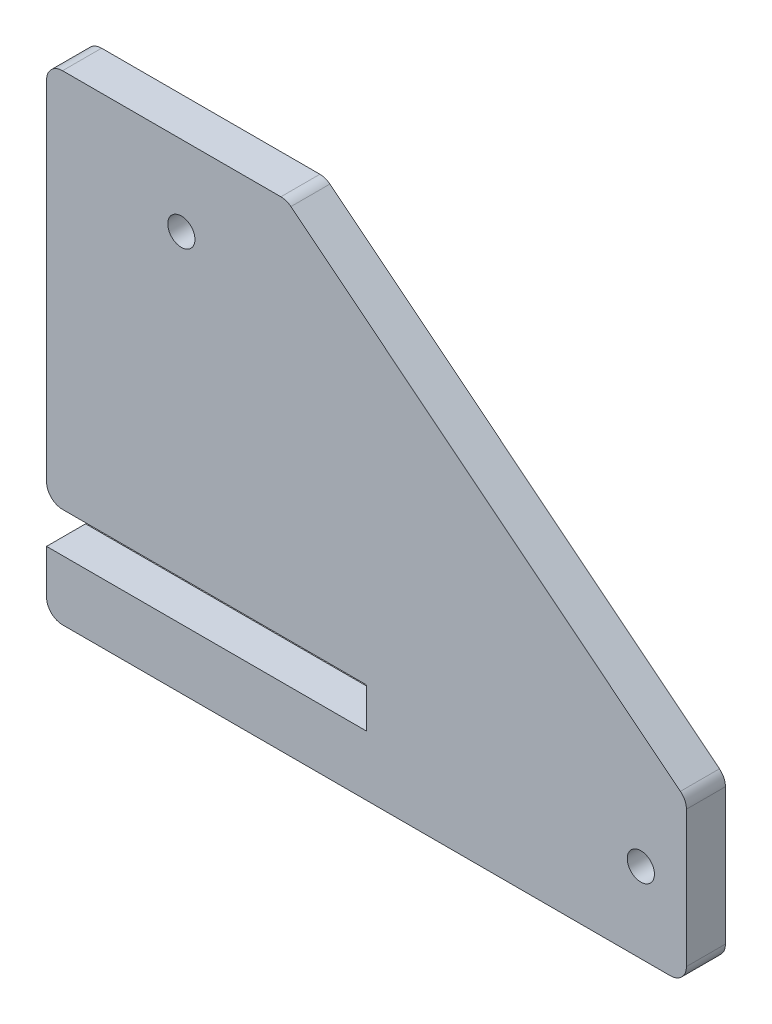
SolidWorks part; units mm, degrees
material "Corrugated Paper"
ref_plane "Front Plane" through (0, 0, 0) normal (0, 0, 1) x (1, 0, 0)
ref_plane "Top Plane" through (0, 0, 0) normal (0, 1, 0) x (1, 0, 0)
ref_plane "Right Plane" through (0, 0, 0) normal (1, 0, 0) x (0, 0, -1)
sketch "Sketch1" plane through (0, 0, 0) normal (0, 0, 1) x (1, 0, 0)
  line L0 (-25.4, 1.5875) -> (-25.4, 6.35)
  line L1 (-25.4, -1.5875) -> (0, -1.5875)
  line L3 (-25.4, 1.5875) -> (0, 1.5875)
  line L4 (0, -1.5875) -> (0, 1.5875)
  line L5 (-25.4, 6.35) -> (25.4, 6.35)
  line L6 (0, 0) -> (25.4, 0) construction
  line L7 (25.4, 6.35) -> (25.4, -6.35)
  line L8 (-25.4, -6.35) -> (25.4, -6.35)
  line L9 (-25.4, -1.5875) -> (-25.4, -6.35)
  line L11 (-25.4, 6.35) -> (25.4, 6.35)
  line L12 (-25.4, 6.35) -> (-25.4, 31.75)
  line L13 (-25.4, 31.75) -> (25.4, 31.75)
  line L14 (25.4, 6.35) -> (25.4, 31.75)
  dimension "D1" = 25.4
  dimension "D2" = 3.175
  dimension "D3" = 25.4
  dimension "D4" = 12.7
  dimension "D5" = 38.1
extrude "Boss-Extrude1" add sketch "Sketch1" along normal mid plane 3.0988 contours L5 L14 L13 L12 | L6 L4 L1 L9 L8 L7 | L4 L6 L7 L5 L0 L3 region at (1.8143, 3.5152, 0) region at (0, 19.05, 0) region at (1.8143, -3.5152, 0)
sketch "Sketch2" plane through (0, 0, 1.5494) normal (0, 0, 1) x (1, 0, 0)
  line L0 (0, 0) -> (25.4, 0) construction
  line L2 (25.4, -6.35) -> (25.4, 31.75) construction
  circle A0 centre (21.7805, 0) radius 1.0795
  dimension "D1" = 2.159
extrude "Cut-Extrude1" cut sketch "Sketch2" against normal through all
sketch "Sketch3" plane through (0, 0, 1.5494) normal (0, 0, 1) x (1, 0, 0)
  circle A0 centre (-14.6975, 25.4) radius 1.0795
  circle A1 centre (21.7805, 0) radius 1.0795 construction
  dimension "D1" = 44.45
  dimension "D2" = 25.4
extrude "Cut-Extrude2" cut sketch "Sketch3" against normal through all
sketch "Sketch4" plane through (0, 0, 1.5494) normal (0, 0, 1) x (1, 0, 0)
  line L0 (-6.35, 31.75) -> (25.4, 6.35)
  line L1 (-25.4, 31.75) -> (25.4, 31.75) construction
  line L2 (25.4, -6.35) -> (25.4, 31.75) construction
  line L3 (-6.35, 31.75) -> (25.4, 31.75)
  line L4 (25.4, 31.75) -> (25.4, 6.35)
  dimension "D1" = 25.4
  dimension "D2" = 31.75
extrude "Cut-Extrude3" cut sketch "Sketch4" against normal through all
fillet "Fillet1" radius 1.27 6 edges at (-25.4, -6.35, 0) (25.4, -6.35, 0) (-25.4, 1.5875, 0) (-25.4, 31.75, 0) (25.4, 6.35, 0) (-6.35, 31.75, 0)
equation "\"D2@Sketch1\"=\"thick\"+\"clear\""
equation "\"D1@Sketch2\" = \"rodThick\""
equation "\"D1@Boss-Extrude1\" = \"thick\""
equation "\"rodThick\"= 0.085in"
equation "\"thick\"= 0.122in"
equation "\"clear\"= 0.003in"
